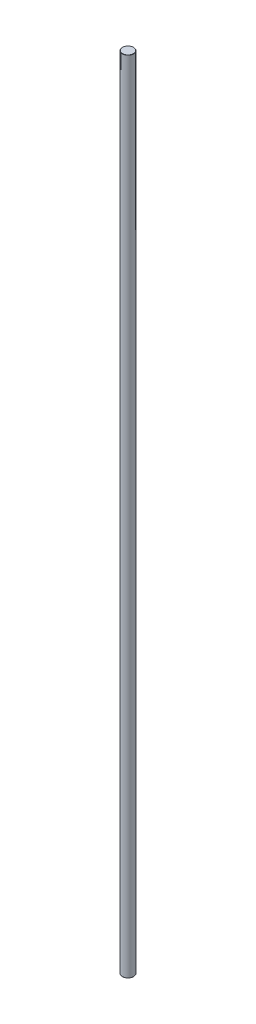
SolidWorks part; units mm, degrees
ref_plane "Ebene vorne" through (0, 0, 0) normal (0, 0, 1) x (1, 0, 0)
ref_plane "Ebene oben" through (0, 0, 0) normal (0, 1, 0) x (1, 0, 0)
ref_plane "Ebene rechts" through (0, 0, 0) normal (1, 0, 0) x (0, 0, -1)
sketch "Skizze1" plane through (0, 0, 0) normal (0, 1, 0) x (1, 0, 0)
  circle A0 centre (0, 0) radius 7
  dimension "D1" = 14
extrude "Aufsatz-Linear austragen1" add sketch "Skizze1" against normal blind 1000
chamfer "Fase1" distance 0.2 angle 45 2 edges at (0, 0, 7) (0, -1000, 7)
ref_axis "Achse1" through (0, -1050, 0) along (0, 1, 0)
